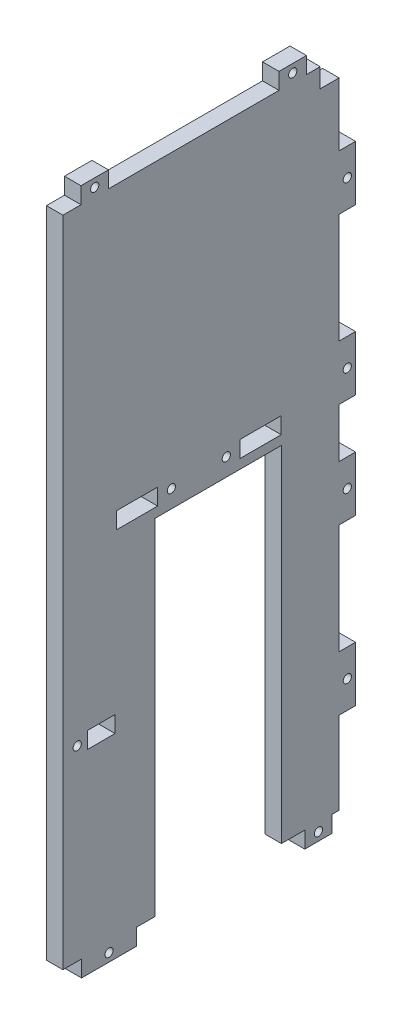
SolidWorks part; units mm, degrees
ref_plane "Plan de face" through (0, 0, 0) normal (0, 0, 1) x (1, 0, 0)
ref_plane "Plan de dessus" through (0, 0, 0) normal (0, 1, 0) x (1, 0, 0)
ref_plane "Plan de droite" through (0, 0, 0) normal (1, 0, 0) x (0, 0, -1)
sketch "Esquisse1" plane through (0, 0, 0) normal (1, 0, 0) x (0, 0, -1)
  line L0 (97.1531, 0) -> (-102.2664, 0) construction
  line L1 (-50.29, 119) -> (50.29, 119)
  line L2 (-50.29, 119) -> (-50.29, -119)
  line L3 (-50.29, -119) -> (50.29, -119)
  line L4 (50.29, 119) -> (50.29, -119)
  line L5 (0, 172.7153) -> (0, -236.1933) construction
  line L7 (-41.29, -48) -> (-31.29, -48)
  line L8 (-41.29, -48) -> (-41.29, -54)
  line L9 (-41.29, -54) -> (-31.29, -54)
  line L10 (-31.29, -48) -> (-31.29, -54)
  line L15 (-30.795, 16) -> (-15.795, 16)
  line L16 (-30.795, 16) -> (-30.795, 10)
  line L17 (-30.795, 10) -> (-15.795, 10)
  line L18 (-15.795, 16) -> (-15.795, 10)
  line L19 (14.205, 16) -> (29.205, 16)
  line L20 (14.205, 16) -> (14.205, 10)
  line L21 (14.205, 10) -> (29.205, 10)
  line L22 (29.205, 16) -> (29.205, 10)
  dimension "D1" = 238
  dimension "D2" = 100.58
  dimension "D4" = 119
  dimension "D13" = 15
  dimension "D14" = 15
  dimension "D15" = 30
  dimension "D16" = 6
  dimension "D17" = 6
  dimension "D3" = 50.29
  dimension "D6" = 19.495
  dimension "D7" = 9
  dimension "D8" = 167
  dimension "D9" = 6
  dimension "D10" = 10
  dimension "D5" = 103
extrude "Boss.-Extru.1" add sketch "Esquisse1" along normal blind 6
sketch "Esquisse3" plane through (6, 0, 0) normal (1, 0, 0) x (0, 0, -1)
  line L0 (-50.29, -119) -> (50.29, -119) construction
  line L1 (-43.5, -119) -> (-23.5, -119)
  line L2 (-43.5, -119) -> (-43.5, -125)
  line L3 (-43.5, -125) -> (-23.5, -125)
  line L4 (-23.5, -119) -> (-23.5, -125)
  line L5 (245.3741, 0) -> (-166.5298, 0) construction
  line L6 (50.29, -119) -> (50.29, 119) construction
  line L7 (37.79, -119) -> (47.79, -119)
  line L8 (37.79, -119) -> (37.79, -125)
  line L9 (37.79, -125) -> (47.79, -125)
  line L10 (0, 208.6671) -> (0, -232.3841) construction
  line L12 (47.79, -119) -> (47.79, -125)
  line L13 (56.29, 29) -> (56.29, 9)
  line L14 (50.29, 9) -> (56.29, 9)
  line L15 (50.29, 29) -> (50.29, 9)
  line L16 (50.29, 29) -> (56.29, 29)
  line L17 (56.29, 89) -> (56.29, 69)
  line L18 (50.29, 69) -> (56.29, 69)
  line L19 (50.29, 89) -> (50.29, 69)
  line L20 (50.29, 89) -> (56.29, 89)
  line L21 (50.29, 119) -> (-50.29, 119) construction
  line L22 (50.29, -89) -> (56.29, -89)
  line L23 (50.29, -89) -> (50.29, -69)
  line L24 (50.29, -69) -> (56.29, -69)
  line L25 (56.29, -89) -> (56.29, -69)
  line L26 (50.29, -29) -> (56.29, -29)
  line L27 (50.29, -29) -> (50.29, -9)
  line L28 (50.29, -9) -> (56.29, -9)
  line L29 (0, -208.6671) -> (0, 232.3841) construction
  line L30 (-50.29, 119) -> (-50.29, -119) construction
  line L34 (50.29, -119) -> (50.29, 119) construction
  line L35 (56.29, -29) -> (56.29, -9)
  line L36 (38.41, 119) -> (28.41, 119)
  line L37 (38.41, 119) -> (38.41, 125)
  line L38 (38.41, 125) -> (28.41, 125)
  line L39 (28.41, 119) -> (28.41, 125)
  line L40 (-50.29, 119) -> (-50.29, -119) construction
  line L41 (-33.71, 119) -> (-43.71, 119)
  line L42 (-33.71, 119) -> (-33.71, 125)
  line L43 (-33.71, 125) -> (-43.71, 125)
  line L44 (-43.71, 119) -> (-43.71, 125)
  dimension "D2" = 20
  dimension "D3" = 6
  dimension "D4" = 10
  dimension "D5" = 6.79
  dimension "D6" = 6
  dimension "D7" = 6
  dimension "D8" = 20
  dimension "D9" = 6
  dimension "D10" = 20
  dimension "D11" = 2.5
  dimension "D14" = 30
  dimension "D15" = 40
  dimension "D16" = 6
  dimension "D17" = 10
  dimension "D18" = 11.88
  dimension "D19" = 6.58
  dimension "D20" = 10
  dimension "D21" = 6
extrude "Boss.-Extru.5" add sketch "Esquisse3" against normal blind 6
sketch "Esquisse6" plane through (6, 0, 0) normal (1, 0, 0) x (0, 0, -1)
  line L0 (-23.5, -119) -> (37.79, -119) construction
  line L1 (-16.71, -119) -> (29.29, -119)
  line L2 (-16.71, -119) -> (-16.71, 6.59)
  line L3 (-16.71, 6.59) -> (29.29, 6.59)
  line L4 (29.29, -119) -> (29.29, 6.59)
  line L5 (50.29, -69) -> (50.29, -29) construction
  line L8 (28.41, 119) -> (-33.71, 119) construction
  dimension "D1" = 46
  dimension "D2" = 112.41
  dimension "D3" = 21
extrude "Enlèv. mat.-Extru.2" cut sketch "Esquisse6" against normal blind 6
sketch "Esquisse7" plane through (0, 0, 0) normal (-1, 0, 0) x (0, 0, 1)
  line L1 (-50.29, 119) -> (-43.41, 119)
  line L2 (-50.29, 119) -> (-50.29, 112)
  line L3 (-50.29, 112) -> (-43.41, 112)
  line L4 (-43.41, 119) -> (-43.41, 112)
  dimension "D1" = 7
  dimension "D2" = 6.88
extrude "Enlèv. mat.-Extru.3" cut sketch "Esquisse7" against normal blind 6
sketch "Esquisse8" plane through (0, 0, 0) normal (-1, 0, 0) x (0, 0, 1)
  line L0 (-51.0214, 13) -> (44.3386, 13) construction
  line L1 (43.5, -125) -> (23.5, -125) construction
  line L4 (30.795, 10) -> (15.795, 10) construction
  line L5 (60.5401, -51) -> (10.4957, -51) construction
  line L6 (41.29, -48) -> (41.29, -54) construction
  line L8 (41.29, -54) -> (31.29, -54) construction
  line L9 (53.2872, 122) -> (-67.0711, 122) construction
  line L10 (33.71, 125) -> (43.71, 125) construction
  line L11 (-28.41, 125) -> (-28.41, 119) construction
  line L12 (33.71, 119) -> (33.71, 125) construction
  line L13 (-67.0711, -122) -> (72.8873, -122) construction
  line L14 (15.795, 10) -> (15.795, 16) construction
  line L15 (-14.205, 16) -> (-14.205, 10) construction
  line L16 (-37.79, -119) -> (-37.79, -125) construction
  line L17 (23.5, -125) -> (23.5, -119) construction
  line L18 (-53.29, 135.0788) -> (-53.29, -173.0788) construction
  line L19 (-56.29, 69) -> (-56.29, 89) construction
  line L21 (-56.29, -69) -> (-50.29, -69) construction
  line L22 (-50.29, 9) -> (-56.29, 9) construction
  line L23 (-56.29, 89) -> (-50.29, 89) construction
  circle A1 centre (-9.205, 13) radius 1.5
  circle A2 centre (10.795, 13) radius 1.5
  circle A5 centre (45.08, -51) radius 1.5
  circle A6 centre (38.71, 122) radius 1.5
  circle A7 centre (-33.41, 122) radius 1.5
  circle A8 centre (33.5, -122) radius 1.5
  circle A9 centre (-53.29, 79) radius 1.5
  circle A10 centre (-42.79, -122) radius 1.5
  circle A11 centre (-53.29, 19) radius 1.5
  circle A12 centre (-53.29, -79) radius 1.5
  circle A13 centre (-53.29, -19) radius 1.5
  point P8 (23.295, 10)
  dimension "D1" = 3
  dimension "D2" = 3
  dimension "D4" = 3
  dimension "D5" = 3
  dimension "D6" = 5
  dimension "D7" = 5
  dimension "D10" = 3
  dimension "D15" = 3
  dimension "D16" = 3
  dimension "D17" = 5
  dimension "D18" = 5
  dimension "D20" = 3
  dimension "D21" = 3
  dimension "D22" = 3
  dimension "D23" = 3
  dimension "D24" = 5
  dimension "D25" = 10
  dimension "D26" = 3
  dimension "D27" = 3
  dimension "D28" = 3
  dimension "D29" = 10
  dimension "D31" = 10
  dimension "D32" = 10
  dimension "D11" = 3.79
  dimension "D13" = 3
  dimension "D14" = 3
  dimension "D30" = 10
extrude "Enlèv. mat.-Extru.4" cut sketch "Esquisse8" against normal blind 6
equation "\"D3@Esquisse1\"=\"D2@Esquisse1\"/2"
equation "\"D4@Esquisse1\"=\"D1@Esquisse1\"/2"
